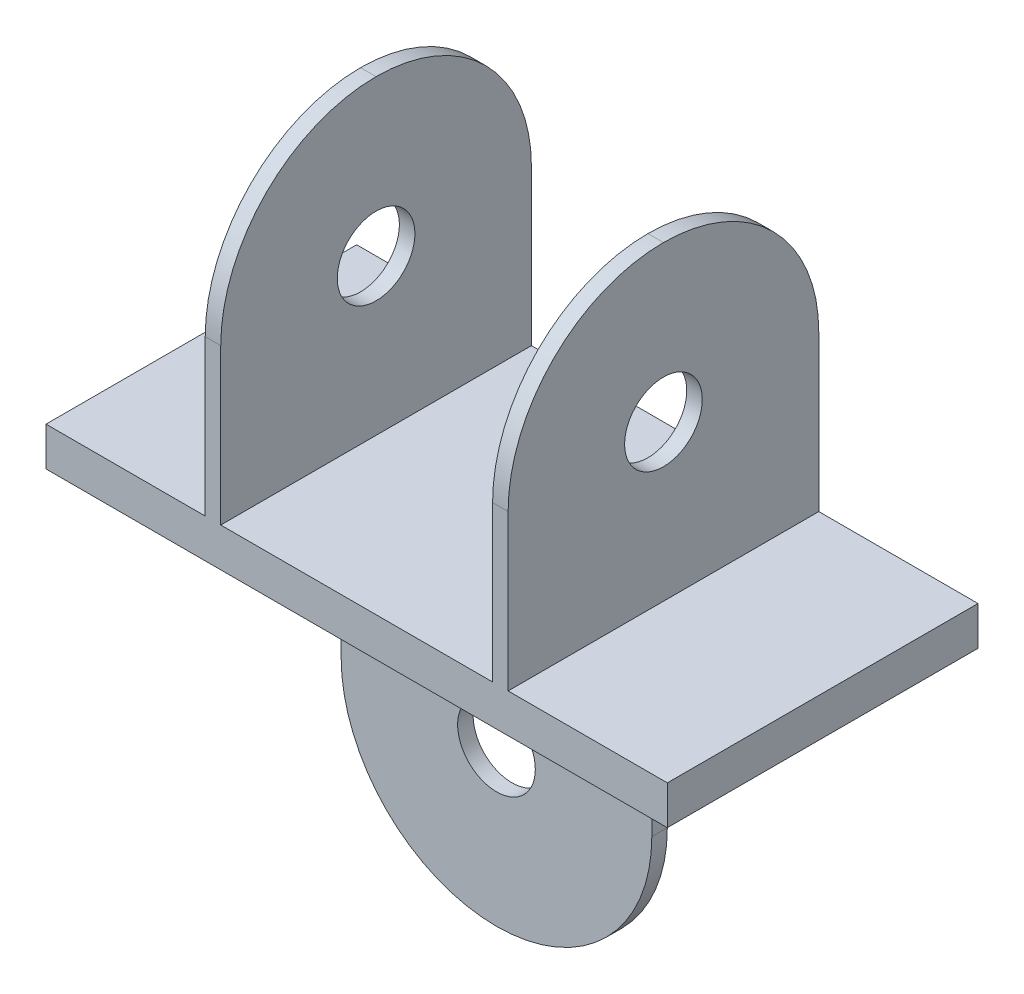
SolidWorks part; units mm, degrees
ref_plane "Front Plane" through (0, 0, 0) normal (0, 0, 1) x (1, 0, 0)
ref_plane "Top Plane" through (0, 0, 0) normal (0, 1, 0) x (1, 0, 0)
ref_plane "Right Plane" through (0, 0, 0) normal (1, 0, 0) x (0, 0, -1)
sketch "Sketch3" plane through (0, 0, 0) normal (0, 0, 1) x (1, 0, 0)
  line L1 (-20, 0) -> (20, 0)
  line L2 (-20, 0) -> (-20, -20)
  line L4 (20, 0) -> (20, -20)
  arc A0 (-20, -20) -> (20, -20) centre (0, -20) ccw
  point P4 (0, 0)
  dimension "D2" = 20
  dimension "D4" = 20
  dimension "D1" = 40
  dimension "D3" = 20
extrude "Boss-Extrude1" add sketch "Sketch3" along normal blind 2
sketch "Sketch4" plane through (0, 0, 0) normal (0, 0, 1) x (1, 0, 0)
  line L1 (-40, 0) -> (40, 0)
  line L2 (-40, 0) -> (-40, 5)
  line L3 (-40, 5) -> (40, 5)
  line L4 (40, 0) -> (40, 5)
  point P4 (0, 0)
  dimension "D1" = 5
  dimension "D2" = 80
extrude "Boss-Extrude2" add sketch "Sketch4" along normal mid plane 40
sketch "Sketch5" plane through (0, 5, 0) normal (0, 1, 0) x (1, 0, 0)
  line L0 (40, 20) -> (-40, 20) construction
  line L1 (-19.5, 20) -> (-17.5, 20)
  line L2 (-19.5, 20) -> (-19.5, -20)
  line L3 (-19.5, -20) -> (-17.5, -20)
  line L4 (-17.5, 20) -> (-17.5, -20)
  line L5 (40, -20) -> (-40, -20) construction
  line L7 (17.5, -20) -> (19.5, -20)
  line L8 (17.5, -20) -> (17.5, 20)
  line L9 (17.5, 20) -> (19.5, 20)
  line L10 (19.5, -20) -> (19.5, 20)
  dimension "D1" = 2
  dimension "D2" = 2
  dimension "D3" = 17.5
  dimension "D4" = 17.5
extrude "Boss-Extrude3" add sketch "Sketch5" along normal blind 40
fillet "Fillet1" radius 20 4 edges at (-18.5, 45, -20) (18.5, 45, -20) (-18.5, 45, 20) (18.5, 45, 20)
sketch "Sketch6" plane through (-19.5, 0, 0) normal (-1, 0, 0) x (0, 0, 1)
  line L0 (20, 25) -> (20, 5) construction
  line L1 (-20, 5) -> (20, 5) construction
  circle A0 centre (0, 25) radius 5
  dimension "D1" = 10
  dimension "D2" = 20
  dimension "D3" = 20
extrude "Cut-Extrude1" cut sketch "Sketch6" against normal blind 80
sketch "Sketch7" plane through (0, 0, 2) normal (0, 0, 1) x (1, 0, 0)
  line L0 (-20, 0) -> (-20, -20) construction
  line L1 (-40, 0) -> (40, 0) construction
  circle A0 centre (0, -20) radius 5
  dimension "D1" = 10
  dimension "D2" = 20
  dimension "D3" = 20
extrude "Cut-Extrude2" cut sketch "Sketch7" against normal blind 80
